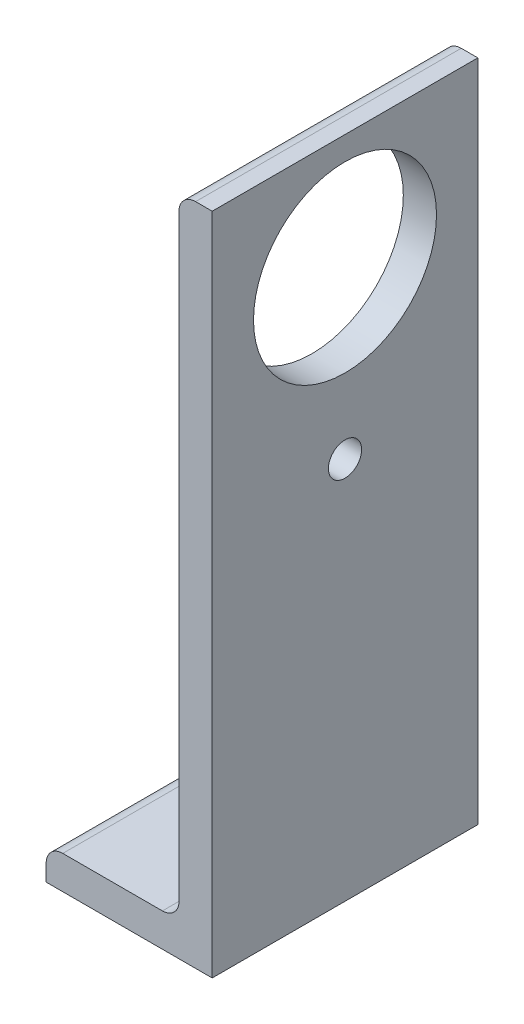
SolidWorks part; units mm, degrees
ref_plane "Front Plane" through (0, 0, 0) normal (0, 0, 1) x (1, 0, 0)
ref_plane "Top Plane" through (0, 0, 0) normal (0, 1, 0) x (1, 0, 0)
ref_plane "Right Plane" through (0, 0, 0) normal (1, 0, 0) x (0, 0, -1)
sketch "Sketch2" plane through (0, 0, 0) normal (0, 0, 1) x (1, 0, 0)
  line L0 (-15.875, 0) -> (15.875, 0)
  line L1 (15.875, 0) -> (15.875, 127)
  line L2 (15.875, 127) -> (9.525, 127) construction
  line L3 (9.525, 123.825) -> (9.525, 9.525)
  line L4 (6.35, 6.35) -> (-12.7, 6.35)
  line L5 (-15.875, 0) -> (-15.875, 6.35) construction
  line L6 (12.7, 127) -> (15.875, 127)
  line L7 (-15.875, 3.175) -> (-15.875, 0)
  arc A0 (9.525, 123.825) -> (12.7, 127) centre (12.7, 123.825) cw
  arc A1 (-15.875, 3.175) -> (-12.7, 6.35) centre (-12.7, 3.175) cw
  arc A2 (9.525, 9.525) -> (6.35, 6.35) centre (6.35, 9.525) cw
  dimension "Vert" = 127
  dimension "Horz" = 31.75
  dimension "Thickness" = 6.35
extrude "Boss-Extrude1" add sketch "Sketch2" along normal mid plane 50.8
ref_plane "Contact Plane 1" through (0, 6.35, 0) normal (0, 1, 0) x (1, 0, 0)
ref_plane "Contact Plane 2" through (9.525, 0, 0) normal (-1, 0, 0) x (0, 0, 1)
sketch "Sketch3" plane through (0, 0, 0) normal (0, -1, 0) x (1, 0, 0)
  line L0 (15.875, 0) -> (-15.875, 0) construction
  line L1 (15.875, 25.4) -> (15.875, -25.4) construction
  line L2 (-15.875, 25.4) -> (-15.875, -25.4) construction
  circle A0 centre (-4.826, 0) radius 4.765
  dimension "D1" = 9.53
  dimension "D2" = 20.701
extrude "Cut-Extrude1" cut sketch "Sketch3" against normal through all contours A0
sketch "Sketch5" plane through (15.875, 0, 0) normal (1, 0, 0) x (0, 0, -1)
  line L0 (-25.4, 0) -> (-25.4, 127) construction
  circle A0 centre (0, 105) radius 17.5
  circle A1 centre (0, 73.25) radius 3.175
  dimension "D1" = 25.4
  dimension "D2" = 105
  dimension "D3" = 35
  dimension "D4" = 31.75
  dimension "D5" = 6.35
extrude "Cut-Extrude2" cut sketch "Sketch5" against normal blind 12.7
